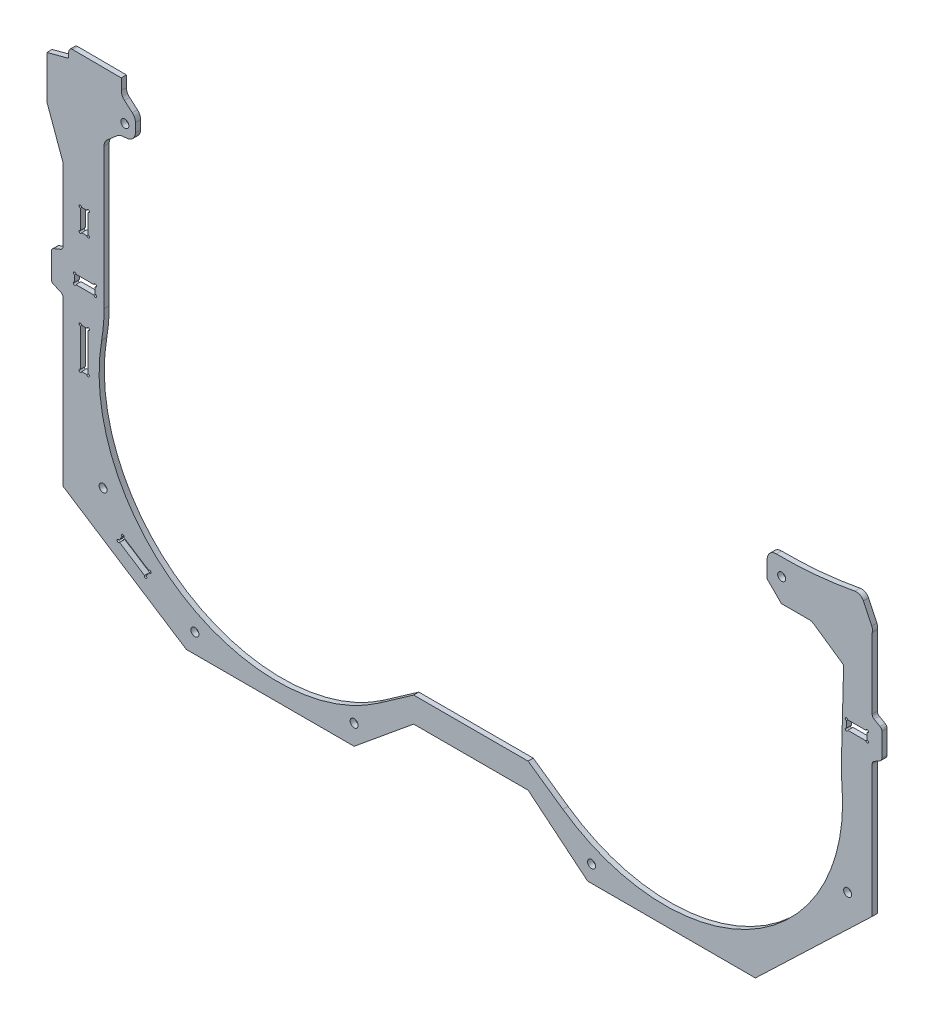
SolidWorks part; units mm, degrees
material "PPS"
ref_plane "前视基准面" through (0, 0, 0) normal (0, 0, 1) x (1, 0, 0)
ref_plane "上视基准面" through (0, 0, 0) normal (0, 1, 0) x (1, 0, 0)
ref_plane "右视基准面" through (0, 0, 0) normal (1, 0, 0) x (0, 0, -1)
sketch "草图1" plane through (0, 0, 0) normal (0, 0, 1) x (1, 0, 0)
  line L0 (-816.4831, 0) -> (39952.7477, 0) construction
  line L1 (0, 10.8762) -> (0, -592.6628) construction
  line L2 (0, 0) -> (206.9686, -284.8678) construction
  line L9 (155.1848, -135.6229) -> (110.024, -178.8146)
  line L10 (110.024, -178.8146) -> (45.146, -178.8146)
  line L60 (-110.024, -178.8146) -> (-45.146, -178.8146)
  line L119 (-135.8935, -19.3983) -> (-141.8504, -24.5203)
  line L187 (152.75, -77.5) -> (145.75, -77.5) construction
  line L188 (152.75, -77.5) -> (152.75, -75) construction
  line L189 (145.75, -77.5) -> (145.75, -75) construction
  line L190 (152.75, -75) -> (145.75, -75) construction
  line L191 (-145.75, -75) -> (-152.75, -75) construction
  line L192 (-152.75, -75) -> (-152.75, -77.5) construction
  line L193 (-152.75, -77.5) -> (-145.75, -77.5) construction
  line L194 (-145.75, -77.5) -> (-145.75, -75) construction
  line L195 (145.25, -74.5) -> (153.25, -74.5)
  line L196 (153.25, -74.5) -> (153.25, -78)
  line L197 (153.25, -78) -> (145.25, -78)
  line L198 (145.25, -78) -> (145.25, -74.5)
  line L199 (-153.25, -78) -> (-145.25, -78)
  line L200 (-153.25, -74.5) -> (-153.25, -78)
  line L201 (-145.25, -74.5) -> (-153.25, -74.5)
  line L202 (-145.25, -78) -> (-145.25, -74.5)
  line L204 (-135.1929, 0) -> (-155.5041, 0.108)
  line L205 (-155.5041, 3.8169) -> (-155.5041, -3.6009) construction
  line L206 (-155.5041, 0.108) -> (-155.5041, -3.6009)
  line L207 (-155.5041, -3.6009) -> (-163.9299, -5.8429)
  line L208 (-155.5041, -3.6009) -> (-170.0041, -7.4592) construction
  line L209 (-163.9299, -5.8429) -> (-163.9299, -22.4613)
  line L210 (-163.9299, -22.4613) -> (-157.7253, -39.5836)
  line L211 (-157.7253, -39.5836) -> (-157.7253, -148.0115)
  line L212 (-157.7253, -148.0115) -> (-110.024, -178.8146)
  line L215 (114.5778, -32.685) -> (114.5778, -42.9165)
  line L216 (120.0778, -48.4165) -> (131.782, -48.4165)
  line L217 (131.782, -48.4165) -> (144.1391, -56.9362)
  line L219 (151.7709, -31.6811) -> (155.0114, -38.4796)
  line L220 (155.1848, -40.6053) -> (155.1848, -135.6229)
  line L221 (120.1823, -39.335) -> (149.4323, -39.335) construction
  line L222 (92.9352, -48.4165) -> (142.5788, -48.4165) construction
  line L223 (75, -103.2286) -> (164.6276, -103.2286) construction
  line L224 (75, -103.2286) -> (35.5666, -159.5453) construction
  line L226 (35.5666, -159.5453) -> (22.126, -150.1341)
  line L227 (22.126, -150.1341) -> (-22.126, -150.1341)
  line L228 (22.126, -159.8702) -> (-22.126, -159.8702)
  line L229 (22.126, -159.8702) -> (45.146, -178.8146)
  line L230 (-35.5666, -159.5453) -> (-22.126, -150.1341)
  line L231 (-22.126, -159.8702) -> (-45.146, -178.8146)
  line L233 (114.5778, -42.9165) -> (120.0778, -48.4165)
  line L234 (75, -103.2286) -> (143.1618, -94.255) construction
  line L235 (144.1391, -56.9362) -> (143.1618, -94.255)
  line L236 (143.1618, -94.255) -> (143.1618, -60.7022) construction
  line L238 (-141.8504, -87.1793) -> (-75, -103.2286) construction
  line L239 (-75, -103.2286) -> (-143.75, -103.2286) construction
  line L240 (-141.8504, -24.5203) -> (-141.8504, -87.1793)
  line L241 (-135.1929, 0) -> (-135.1929, -5.85)
  line L242 (-135.1929, -5.85) -> (-129.7197, -10.5767)
  line L243 (-129.7197, -10.5767) -> (-129.7197, -18.7984)
  line L244 (-129.7197, -18.7984) -> (-135.8935, -19.3983)
  circle A76 centre (75, -103.2286) radius 68.75 construction
  circle A78 centre (-133.8062, -14.6009) radius 1.55
  arc A79 (155.0114, -38.4796) -> (155.1848, -40.6053) centre (152.3033, -39.7704) cw
  circle A80 centre (-75, -103.2286) radius 68.75 construction
  arc A81 (148.5011, -30.0249) -> (151.7709, -31.6811) centre (149.0628, -32.9719) cw
  arc A82 (153.902, -42.309) -> (155.0114, -38.4796) centre (152.3033, -39.7704) ccw construction
  arc A83 (148.5011, -30.0249) -> (114.5778, -32.685) centre (119.5082, 122.0773) cw
  arc A84 (97.7907, -31.2329) -> (148.5011, -30.0249) centre (119.5082, 122.0773) ccw construction
  circle A85 centre (149.4323, -39.335) radius 1.55 construction
  circle A86 centre (120.1823, -39.335) radius 1.55
  arc A87 (35.5666, -159.5453) -> (143.75, -103.2286) centre (75, -103.2286) ccw
  arc A88 (-35.5666, -159.5453) -> (-143.75, -103.2286) centre (-75, -103.2286) cw
  arc A89 (143.1618, -94.255) -> (143.75, -103.2286) centre (75, -103.2286) cw
  arc A91 (-143.75, -103.2286) -> (-141.8504, -87.1793) centre (-75, -103.2286) cw
  point P10 (149.25, -75)
  point P29 (0, -150.1341)
  point P32 (110.024, -178.8146)
  point P38 (153.25, -76.25)
  point P92 (0, -159.8702)
  dimension "D1" = 36
  dimension "D2" = 75
  dimension "D3" = 137.5
  dimension "D6" = 75
  dimension "D7" = 149.25
  dimension "D15" = 125
  dimension "D14" = 3.1
  dimension "D4" = 2.5
  dimension "D5" = 7
  dimension "D8" = 7
  dimension "D9" = 0.5
  dimension "D10" = 0.5
  dimension "D11" = 0.5
  dimension "D12" = 0.5
  dimension "D13" = 29.25
  dimension "D16" = 7.5
  dimension "D17" = 1.5
  dimension "D18" = 13.5
extrude "凸台-拉伸1" add sketch "草图1" along normal blind 2
sketch "草图2" plane through (0, 0, 0) normal (0, 0, 1) x (1, 0, 0)
  line L0 (155.1848, -68.75) -> (158.9348, -70.9151)
  line L1 (155.1848, -135.6229) -> (155.1848, -40.6053) construction
  line L2 (158.9348, -70.9151) -> (158.9348, -81.5849)
  line L3 (158.9348, -81.5849) -> (155.1848, -83.75)
  line L4 (155.1848, -83.75) -> (155.1848, -68.75)
  line L5 (153.25, -76.25) -> (184.2947, -76.25) construction
  line L6 (153.25, -78) -> (153.25, -74.5) construction
  line L7 (-153.25, -76.25) -> (-171.2105, -76.25) construction
  line L8 (-153.25, -74.5) -> (-153.25, -78) construction
  line L9 (-157.7253, -68.75) -> (-157.7253, -83.75)
  line L10 (-157.7253, -39.5836) -> (-157.7253, -148.0115) construction
  line L11 (-157.7253, -83.75) -> (-162.2253, -81.886)
  line L12 (-162.2253, -81.886) -> (-162.2253, -70.614)
  line L13 (-162.2253, -70.614) -> (-157.7253, -68.75)
  dimension "D1" = 3.75
  dimension "D2" = 7.5
  dimension "D3" = 60
  dimension "D4" = 67.5
  dimension "D5" = 4.5
extrude "凸台-拉伸2" add sketch "草图2" against normal up to surface from surface up to face at (-132.2562, -14.6009, 0) starting at face at (149.25, -76.25, 2)
fillet "圆角1" radius 66.25 2 edges at (-141.8504, -87.1793, 1) (143.1618, -94.255, 1)
fillet "圆角4" radius 1.5 9 edges at (155.1848, -68.75, 1) (158.9348, -70.9151, 1) (155.1848, -83.75, 1) (158.9348, -81.5849, 1) (-155.5041, 0.108, 1) (-157.7253, -68.75, 1) (-162.2253, -70.614, 1) (-162.2253, -81.886, 1) (-157.7253, -83.75, 1)
sketch "板状设备接口" plane through (0, 0, 2) normal (0, 0, 1) x (1, 0, 0)
  line L0 (-151, -90.5) -> (-148, -90.5)
  line L1 (-148, -90.5) -> (-148, -106)
  line L2 (-148, -106) -> (-151, -106)
  line L3 (-151, -106) -> (-151, -90.5)
  line L4 (-148, -77.5) -> (-148, -75) construction
  line L5 (-151, -75) -> (-151, -77.5) construction
  line L6 (-151, -51) -> (-148, -51)
  line L7 (-148, -51) -> (-148, -59.5)
  line L8 (-148, -59.5) -> (-151, -59.5)
  line L9 (-151, -59.5) -> (-151, -51)
  line L10 (-145.25, -74.5) -> (-153.25, -74.5) construction
  line L11 (-153.25, -78) -> (-145.25, -78) construction
  line L12 (-134.6497, -153.092) -> (-124.1488, -159.8729)
  line L13 (-124.1488, -159.8729) -> (-125.7762, -162.3931)
  line L14 (-125.7762, -162.3931) -> (-136.2771, -155.6122)
  line L15 (-136.2771, -155.6122) -> (-134.6497, -153.092)
  line L21 (-157.7253, -148.0115) -> (-110.024, -178.8146) construction
  line L22 (-131.0266, -159.0026) -> (-133.8746, -163.413) construction
  dimension "D1" = 15
  dimension "D2" = 8.5
  dimension "D3" = 12.5
  dimension "D4" = 15.5
  dimension "D5" = 5.25
  dimension "D6" = 12.5
  dimension "D7" = 3
extrude "设备接口" cut sketch "板状设备接口" against normal through all
sketch "草图4" plane through (0, 0, 0) normal (0, 0, 1) x (1, 0, 0)
  line L0 (-157.7253, -84.7523) -> (-157.7253, -148.0115) construction
  line L1 (-110.024, -178.8146) -> (-45.146, -178.8146) construction
  line L2 (155.1848, -135.6229) -> (155.1848, -84.616) construction
  line L3 (-45.146, -171.0646) -> (-45.146, -178.8146) construction
  line L4 (45.146, -178.8146) -> (110.024, -178.8146) construction
  circle A0 centre (-142.2253, -140.8215) radius 1.55
  circle A1 centre (-45.146, -171.0646) radius 1.55
  circle A2 centre (-106.713, -171.3146) radius 1.55
  circle A3 centre (46.656, -172.3146) radius 1.55
  circle A4 centre (145.6848, -132.301) radius 1.55
  dimension "D5" = 3.1
  dimension "D1" = 15.5
  dimension "D2" = 7.5
  dimension "D3" = 7.75
  dimension "D4" = 9.5
  dimension "D6" = 6.5
extrude "切除-拉伸3" cut sketch "草图4" along normal through all
fillet "圆角5" radius 3.5 7 edges at (131.782, -48.4165, 1) (114.5778, -32.685, 1) (-141.8504, -24.5203, 1) (-129.7197, -10.5767, 1) (-135.1929, -5.85, 1) (-135.8935, -19.3983, 1) (-129.7197, -18.7984, 1)
sketch "过切除" plane through (0, 0, 0) normal (0, 0, 1) x (1, 0, 0)
  circle A0 centre (-151, -51) radius 0.5
  circle A1 centre (-148, -51) radius 0.5
  circle A2 centre (-151, -59.5) radius 0.5
  circle A3 centre (-148, -59.5) radius 0.5
  circle A4 centre (-153.25, -74.5) radius 0.5
  circle A5 centre (-145.25, -74.5) radius 0.5
  circle A6 centre (-145.25, -78) radius 0.5
  circle A7 centre (-153.25, -78) radius 0.5
  circle A8 centre (-151, -90.5) radius 0.5
  circle A9 centre (-148, -90.5) radius 0.5
  circle A10 centre (-151, -106) radius 0.5
  circle A11 centre (-148, -106) radius 0.5
  circle A12 centre (-134.6497, -153.092) radius 0.5
  circle A13 centre (-136.2771, -155.6122) radius 0.5
  circle A14 centre (-124.1488, -159.8729) radius 0.5
  circle A15 centre (-125.7762, -162.3931) radius 0.5
  circle A16 centre (145.25, -74.5) radius 0.5
  circle A17 centre (153.25, -74.5) radius 0.5
  circle A18 centre (153.25, -78) radius 0.5
  circle A19 centre (145.25, -78) radius 0.5
  dimension "D1" = 1
extrude "这个是因为刀的限制不能切直角" cut sketch "过切除" along normal through all
